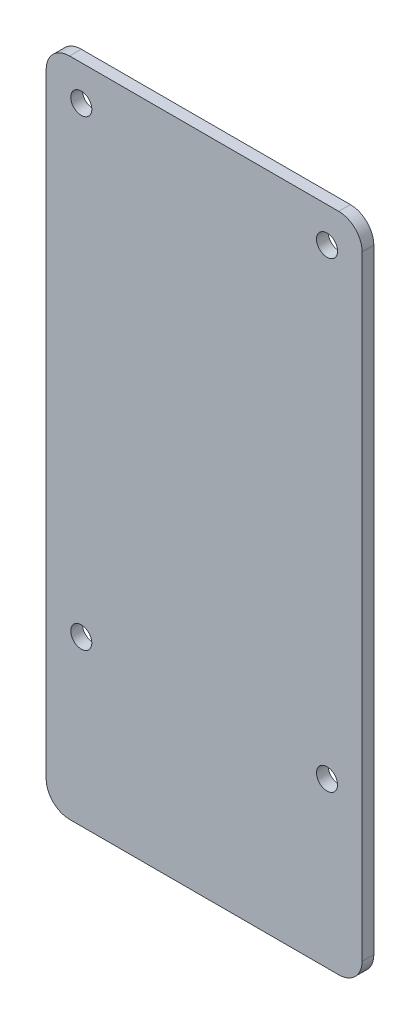
SolidWorks part; units mm, degrees
ref_plane "Piano frontale" through (0, 0, 0) normal (0, 0, 1) x (1, 0, 0)
ref_plane "Piano superiore" through (0, 0, 0) normal (0, 1, 0) x (1, 0, 0)
ref_plane "Piano destro" through (0, 0, 0) normal (1, 0, 0) x (0, 0, -1)
sketch "Sketch1" plane through (0, 0, 0) normal (0, 0, 1) x (1, 0, 0)
  line L0 (-140, 89) -> (-94, 89) construction
  line L1 (-90, 85) -> (-90, -20) construction
  line L2 (-94, -24) -> (-140, -24) construction
  line L3 (-144, -20) -> (-144, 85) construction
  line L4 (-140, 89) -> (-94, 89)
  line L5 (-90, 85) -> (-90, -20)
  line L6 (-94, -24) -> (-140, -24)
  line L7 (-144, -20) -> (-144, 85)
  arc A0 (-90, 85) -> (-94, 89) centre (-94, 85) ccw construction
  arc A1 (-94, -24) -> (-90, -20) centre (-94, -20) ccw construction
  arc A2 (-144, -20) -> (-140, -24) centre (-140, -20) ccw construction
  arc A3 (-140, 89) -> (-144, 85) centre (-140, 85) ccw construction
  arc A4 (-90, 85) -> (-94, 89) centre (-94, 85) ccw
  arc A5 (-94, -24) -> (-90, -20) centre (-94, -20) ccw
  arc A6 (-144, -20) -> (-140, -24) centre (-140, -20) ccw
  arc A7 (-140, 89) -> (-144, 85) centre (-140, 85) ccw
extrude "Boss-Extrude1" add sketch "Sketch1" along normal blind 2
sketch "Sketch2" plane through (0, 0, -12.5682) normal (0, 0, -1) x (-1, 0, 0)
  circle A0 centre (96, 83) radius 1.8 construction
  circle A1 centre (96, 83) radius 1.8
  circle A2 centre (138, 83) radius 1.8 construction
  circle A3 centre (138, 83) radius 1.8
  circle A7 centre (96, 4) radius 1.8 construction
  circle A8 centre (138, 4) radius 1.8 construction
  circle A9 centre (138, 4) radius 1.8
  circle A10 centre (96, 4) radius 1.8
extrude "Cut-Extrude1" cut sketch "Sketch2" against normal through all both and the other way through all
ref_point "Point1"
ref_point "Point2"
ref_axis "Axis1" through (-117, -24, 2) along (0, 1, 0)
